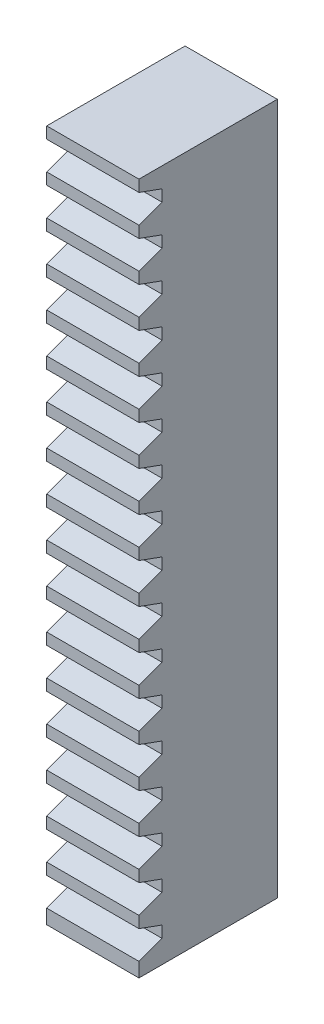
SolidWorks part; units mm, degrees
ref_plane "Alzado" through (0, 0, 0) normal (0, 0, 1) x (1, 0, 0)
ref_plane "Planta" through (0, 0, 0) normal (0, 1, 0) x (1, 0, 0)
ref_plane "Vista lateral" through (0, 0, 0) normal (1, 0, 0) x (0, 0, -1)
sketch "Croquis2" plane through (0, 0, 0) normal (0, 0, 1) x (1, 0, 0)
  line L0 (52.8503, 101.9015) -> (72.8503, 101.9015)
  line L1 (72.8503, 101.9015) -> (72.8503, -28.0985)
  line L15 (52.8503, -98.0985) -> (62.8503, -98.0985)
  line L16 (62.8503, -98.0985) -> (62.8503, -47.8388)
  line L17 (62.8503, -47.8388) -> (92.8503, -47.8388)
  line L18 (92.8503, -47.8388) -> (92.8503, -98.0985)
  line L19 (92.8503, -98.0985) -> (102.8503, -98.0985)
  line L20 (102.8503, -98.0985) -> (102.8503, -28.0985)
  line L21 (102.8503, -28.0985) -> (72.8503, -28.0985)
  line L22 (52.8503, 101.9015) -> (52.8503, -98.0985)
  dimension "D1" = 20
  dimension "D2" = 130
  dimension "D6" = 30
  dimension "D3" = 200
  dimension "D4" = 10
  dimension "D5" = 10
extrude "Saliente-Extruir1" add sketch "Croquis2" along normal blind 30
sketch "Croquis3" plane through (102.8503, 0, 0) normal (1, 0, 0) x (0, 0, -1)
  line L0 (-15, -83.0985) -> (-15, -98.0985) construction
  line L1 (-30, -98.0985) -> (0, -98.0985) construction
  circle A0 centre (-15, -83.0985) radius 6
  dimension "D1" = 15
extrude "Cortar-Extruir1" cut sketch "Croquis3" against normal blind 50
sketch "Croquis4" plane through (102.8503, 0, 0) normal (1, 0, 0) x (0, 0, -1)
  line L4 (-30, -98.0985) -> (0, -98.0985) construction
  line L6 (-30, -98.0985) -> (-30, -28.0985) construction
  line L11 (0, -98.0985) -> (0, -28.0985) construction
  line L14 (-20, -98.0985) -> (-30, -98.0985)
  line L15 (-30, -98.0985) -> (-30, -88.0985)
  line L16 (-10, -98.0985) -> (0, -98.0985)
  line L17 (0, -98.0985) -> (0, -88.0985)
  arc A3 (-30, -88.0985) -> (-20, -98.0985) centre (-20, -88.0985) ccw
  arc A4 (-10, -98.0985) -> (0, -88.0985) centre (-10, -88.0985) ccw
extrude "Cortar-Extruir2" cut sketch "Croquis4" against normal blind 50
sketch "Croquis5" plane through (52.8503, 0, 0) normal (-1, 0, 0) x (0, 0, 1)
  line L1 (30, 101.9015) -> (30, -88.0985) construction
  line L2 (30, 99.4015) -> (25, 97.5817)
  line L3 (25, 97.5817) -> (25, 95.0817)
  line L4 (25, 95.0817) -> (30, 93.2618)
  line L5 (30, 93.2618) -> (30, 99.4015)
  line L7 (30, 90.7618) -> (25, 88.942)
  line L8 (25, 88.942) -> (25, 86.442)
  line L9 (25, 86.442) -> (30, 84.6221)
  line L10 (30, 84.6221) -> (30, 90.7618)
  line L12 (30, 82.1221) -> (25, 80.3023)
  line L13 (25, 80.3023) -> (25, 77.8023)
  line L14 (25, 77.8023) -> (30, 75.9824)
  line L15 (30, 75.9824) -> (30, 82.1221)
  line L17 (30, 73.4824) -> (25, 71.6626)
  line L18 (25, 71.6626) -> (25, 69.1626)
  line L19 (25, 69.1626) -> (30, 67.3427)
  line L20 (30, 67.3427) -> (30, 73.4824)
  line L22 (30, 64.8427) -> (25, 63.0229)
  line L23 (25, 63.0229) -> (25, 60.5229)
  line L24 (25, 60.5229) -> (30, 58.703)
  line L25 (30, 58.703) -> (30, 64.8427)
  line L27 (30, 56.203) -> (25, 54.3831)
  line L28 (25, 54.3831) -> (25, 51.8831)
  line L29 (25, 51.8831) -> (30, 50.0633)
  line L30 (30, 50.0633) -> (30, 56.203)
  line L32 (30, 47.5633) -> (25, 45.7434)
  line L33 (25, 45.7434) -> (25, 43.2434)
  line L34 (25, 43.2434) -> (30, 41.4236)
  line L35 (30, 41.4236) -> (30, 47.5633)
  line L37 (30, 38.9236) -> (25, 37.1037)
  line L38 (25, 37.1037) -> (25, 34.6037)
  line L39 (25, 34.6037) -> (30, 32.7839)
  line L40 (30, 32.7839) -> (30, 38.9236)
  line L42 (30, 30.2839) -> (25, 28.464)
  line L43 (25, 28.464) -> (25, 25.964)
  line L44 (25, 25.964) -> (30, 24.1442)
  line L45 (30, 24.1442) -> (30, 30.2839)
  line L47 (30, 21.6442) -> (25, 19.8243)
  line L48 (25, 19.8243) -> (25, 17.3243)
  line L49 (25, 17.3243) -> (30, 15.5045)
  line L50 (30, 15.5045) -> (30, 21.6442)
  line L52 (30, 13.0045) -> (25, 11.1846)
  line L53 (25, 11.1846) -> (25, 8.6846)
  line L54 (25, 8.6846) -> (30, 6.8648)
  line L55 (30, 6.8648) -> (30, 13.0045)
  dimension "D2" = 2.5
  dimension "D3" = 110
  dimension "D4" = 110
  dimension "D5" = 5
  dimension "D6" = 2.5
extrude "Cortar-Extruir3" cut sketch "Croquis5" against normal blind 20
sketch "Croquis6" plane through (0, 0, 30) normal (0, 0, 1) x (1, 0, 0)
  line L0 (92.8503, -28.0985) -> (102.8503, -28.0985)
  line L2 (102.8503, -88.0985) -> (102.8503, -28.0985) construction
  line L3 (102.8503, -28.0985) -> (102.8503, -38.0985)
  line L4 (102.8503, -28.0985) -> (72.8503, -28.0985) construction
  arc A0 (102.8503, -38.0985) -> (92.8503, -28.0985) centre (92.8503, -38.0985) ccw
extrude "Cortar-Extruir4" cut sketch "Croquis6" against normal blind 30
sketch "Croquis7" plane through (0, 101.9015, 0) normal (0, 1, 0) x (1, 0, 0)
  line L0 (52.8503, 0) -> (52.8503, -30)
  line L1 (52.8503, -30) -> (72.8503, -30)
  line L2 (72.8503, -30) -> (72.8503, 0)
  line L3 (72.8503, 0) -> (52.8503, 0)
extrude "Saliente-Extruir2" add sketch "Croquis7" along normal blind 50
sketch "Croquis8" plane through (52.8503, 0, 0) normal (-1, 0, 0) x (0, 0, 1)
  line L0 (30, 99.4015) -> (30, 101.9015)
  line L1 (30, 151.9015) -> (30, 99.4015) construction
  line L2 (30, 101.9015) -> (25, 103.7214)
  line L3 (25, 103.7214) -> (25, 106.2214)
  line L4 (25, 106.2214) -> (30, 108.0412)
  line L5 (30, 108.0412) -> (30, 101.9015)
  line L6 (30, 108.0412) -> (30, 110.5412)
  line L7 (30, 110.5412) -> (25, 110.5412)
  line L8 (30, 110.5412) -> (25, 112.3611)
  line L9 (25, 112.3611) -> (25, 114.8611)
  line L10 (25, 114.8611) -> (30, 116.6809)
  line L11 (30, 116.6809) -> (30, 110.5412)
  line L12 (30, 119.1809) -> (25, 121.0008)
  line L13 (25, 121.0008) -> (25, 123.5008)
  line L14 (25, 123.5008) -> (30, 125.3206)
  line L15 (30, 125.3206) -> (30, 119.1809)
  line L16 (30, 127.8206) -> (25, 129.6405)
  line L17 (25, 129.6405) -> (25, 132.1405)
  line L18 (25, 132.1405) -> (30, 133.9603)
  line L19 (30, 133.9603) -> (30, 127.8206)
  line L20 (30, 136.4603) -> (25, 138.2802)
  line L21 (25, 138.2802) -> (25, 140.7802)
  line L22 (25, 140.7802) -> (30, 142.6)
  line L23 (30, 142.6) -> (30, 136.4603)
  line L24 (30, 145.1) -> (25, 146.9199)
  line L25 (25, 146.9199) -> (25, 149.4199)
  line L26 (25, 149.4199) -> (30, 151.2397)
  line L27 (30, 151.2397) -> (30, 145.1)
  point P5 (0, 0)
  point P31 (0, 0)
  dimension "D1" = 5
  dimension "D2" = 2.5
  dimension "D3" = 2.5
  dimension "D4" = 110
  dimension "D5" = 110
  dimension "D6" = 2.5
  dimension "D7" = 6
extrude "Cortar-Extruir6" cut sketch "Croquis8" against normal blind 20 contours L27 L26 L25 L24 | L23 L22 L21 L20 | L19 L18 L17 L16 | L15 L14 L13 L12 | L11 L10 L9 L8 | L5 L4 L3 L2 region at (52.8503, 113.6111, 27.8511) region at (52.8503, 104.9714, 27.8511) region at (52.8503, 122.2508, 27.8511) region at (52.8503, 130.8905, 27.8511) region at (52.8503, 139.5302, 27.8511) region at (52.8503, 148.1699, 27.8511)
sketch "Croquis9" plane through (0, 0, 30) normal (0, 0, 1) x (1, 0, 0)
  line L0 (52.8503, -88.0985) -> (62.8503, -88.0985)
  line L1 (62.8503, -88.0985) -> (62.8503, -98.0985)
  line L2 (62.8503, -98.0985) -> (52.8503, -98.0985)
  line L3 (52.8503, -98.0985) -> (52.8503, -88.0985)
  line L4 (92.8503, -88.0985) -> (102.8503, -88.0985)
  line L5 (102.8503, -88.0985) -> (102.8503, -98.0985)
  line L6 (102.8503, -98.0985) -> (92.8503, -98.0985)
  line L7 (92.8503, -98.0985) -> (92.8503, -88.0985)
extrude "Saliente-Extruir3" add sketch "Croquis9" against normal blind 30
sketch "Croquis10" plane through (102.8503, 0, 0) normal (1, 0, 0) x (0, 0, -1)
  line L0 (-30, -28.0985) -> (-30, -98.0985)
  line L1 (-30, -28.0985) -> (0, -28.0985)
  line L2 (0, -28.0985) -> (0, -98.0985)
  line L3 (0, -98.0985) -> (-30, -98.0985)
extrude "Saliente-Extruir4" add sketch "Croquis10" along normal blind 50
sketch "Croquis12" plane through (152.8503, 0, 0) normal (1, 0, 0) x (0, 0, -1)
  line L0 (0, -28.0985) -> (-30, -28.0985)
  line L1 (-30, -28.0985) -> (-30, -98.0985)
  line L2 (-30, -98.0985) -> (0, -98.0985)
  line L3 (0, -98.0985) -> (0, -28.0985)
extrude "Saliente-Extruir5" add sketch "Croquis12" against normal blind 100
sketch "Croquis13" plane through (0, 0, 30) normal (0, 0, 1) x (1, 0, 0)
  line L0 (52.8503, 6.8648) -> (72.8503, 6.8648)
  line L1 (52.8503, 6.8648) -> (52.8503, -98.0985) construction
  line L2 (72.8503, 6.8648) -> (52.8503, 6.8648) construction
  line L3 (72.8503, 6.8648) -> (72.8503, -28.0985)
  line L4 (72.8503, -28.0985) -> (152.8503, -28.0985)
  line L5 (152.8503, -28.0985) -> (152.8503, -98.0985)
  line L6 (152.8503, -98.0985) -> (52.8503, -98.0985)
  line L7 (52.8503, -98.0985) -> (52.8503, 6.8648)
extrude "Saliente-Extruir6" add sketch "Croquis13" along normal blind 80
sketch "Croquis15" plane through (0, -28.0985, 0) normal (0, 1, 0) x (1, 0, 0)
  line L0 (72.8503, 0) -> (152.8503, 0)
  line L1 (72.8503, -110) -> (72.8503, 0) construction
  line L2 (152.8503, 0) -> (72.8503, 0) construction
  line L3 (152.8503, 0) -> (152.8503, -110)
  line L4 (152.8503, -110) -> (72.8503, -110)
  line L5 (72.8503, -110) -> (72.8503, 0)
extrude "Saliente-Extruir7" add sketch "Croquis15" along normal blind 30
sketch "Croquis16" plane through (0, 6.8648, 0) normal (0, 1, 0) x (1, 0, 0)
  line L0 (52.8503, -110) -> (72.8503, -110)
  line L1 (72.8503, -110) -> (72.8503, -30)
  line L2 (72.8503, -30) -> (52.8503, -30)
  line L3 (52.8503, -30) -> (52.8503, -110)
extrude "Cortar-Extruir7" cut sketch "Croquis16" against normal up to vertex (4.9633 mm away) up to point (72.8503, 1.9015, 0)
sketch "Croquis17" plane through (52.8503, 0, 0) normal (-1, 0, 0) x (0, 0, 1)
  line L2 (110, 1.9015) -> (110, -98.0985)
  line L3 (0, -98.0985) -> (77.3858, -98.0985)
  line L4 (30, 1.9015) -> (110, 1.9015)
  line L5 (68.8909, -79.4158) -> (0, -10.5249)
  line L6 (30, 1.9015) -> (90.1041, -58.2026)
  line L7 (0, -10.5249) -> (0, -98.0985)
  line L8 (0, 151.9015) -> (0, -98.0985) construction
  line L10 (77.3858, -98.0985) -> (110, -98.0985)
  arc A1 (68.8909, -79.4158) -> (90.1041, -58.2026) centre (79.4975, -68.8092) ccw
  dimension "D1" = 85
  dimension "D3" = 30
extrude "Cortar-Extruir8" cut sketch "Croquis17" against normal blind 100
sketch "Croquis19" plane through (0, 0, 0) normal (0, 1, 0) x (1, 0, 0)
  line L0 (52.8503, -94.4975) -> (57.8503, -94.4975)
  line L1 (52.8503, -94.4975) -> (152.8503, -94.4975) construction
  line L2 (57.8503, -94.4975) -> (57.8503, -44.1182)
  line L3 (57.8503, -44.1182) -> (88.8503, -44.1182)
  line L4 (88.8503, -44.1182) -> (88.8503, -94.4975)
  line L5 (88.8503, -94.4975) -> (93.8503, -94.4975)
  line L6 (93.8503, -94.4975) -> (93.8503, -30)
  line L7 (152.8503, -30) -> (72.8503, -30) construction
  line L8 (93.8503, -30) -> (93.8503, 4.7181)
  line L9 (93.8503, 4.7181) -> (155.9644, 4.7181)
  line L10 (155.9644, 4.7181) -> (155.9644, -98.5037)
  line L11 (155.9644, -98.5037) -> (93.8503, -98.5037)
  line L13 (52.8503, -30) -> (52.8503, -94.4975)
  line L14 (93.8503, -98.5037) -> (93.8503, -94.4975)
  dimension "D1" = 5
  dimension "D2" = 5
  dimension "D3" = 31
extrude "Cortar-Extruir10" cut sketch "Croquis19" against normal through all both and the other way through all contours L14 L11 L10 L9 L8 L6 region at (124.9074, 0, 46.8928)
sketch "Croquis22" plane through (93.8503, 0, 0) normal (1, 0, 0) x (0, 0, -1)
  line L0 (-90.1041, -58.2026) -> (-68.8909, -79.4158)
  circle A0 centre (-79.4975, -68.8092) radius 6
  dimension "D1" = 12
extrude "Cortar-Extruir14" cut sketch "Croquis22" against normal blind 100 contours L0 A0 | L0 A0 region at (93.8503, -67.0085, 77.6968) region at (93.8503, -70.6098, 81.2981)
sketch "Croquis24" plane through (72.8503, 0, 0) normal (1, 0, 0) x (0, 0, -1)
  line L0 (-30, 151.2397) -> (0, 151.2397)
  line L1 (0, 1.9015) -> (0, 151.9015) construction
  line L2 (0, 151.2397) -> (0, 153.7397)
  line L3 (0, 153.7397) -> (-30, 153.7397)
  line L4 (-30, 153.7397) -> (-30, 151.2397)
  dimension "D1" = 2.5
extrude "Saliente-Extruir8" add sketch "Croquis24" against normal blind 20
ref_plane "Plano3" through (0, 1.9015, 0) normal (0, 1, 0) x (1, 0, 0)
sketch "Croquis25" plane through (0, 1.9015, 0) normal (0, 1, 0) x (1, 0, 0)
  line L0 (52.8503, -94.4975) -> (57.8503, -94.4975)
  line L1 (52.8503, -94.4975) -> (93.8503, -94.4975) construction
  line L2 (57.8503, -94.4975) -> (57.8503, -44.4975)
  line L3 (57.8503, -44.4975) -> (88.8503, -44.4975)
  line L4 (88.8503, -44.4975) -> (88.8503, -94.4975)
  line L5 (88.8503, -94.4975) -> (57.8503, -94.4975)
  line L6 (93.8503, -94.4975) -> (93.8503, -68.8909) construction
  dimension "D1" = 5
  dimension "D2" = 5
  dimension "D3" = 31
  dimension "D4" = 50
extrude "Cortar-Extruir15" cut sketch "Croquis25" against normal blind 100 contours L5 L4 L3 L2 region at (73.3503, 1.9015, 69.4975)
sketch "Croquis26" plane through (0, 15.9508, 15.9508) normal (0, 0.7071, 0.7071) x (1, 0, 0)
  line L3 (88.8503, -104.8686) -> (88.8503, -40.3712) construction
  line L4 (88.8503, -90.3712) -> (57.8503, -90.3712)
  line L5 (57.8503, -40.3712) -> (57.8503, -104.8686) construction
  line L6 (57.8503, -90.3712) -> (57.8503, -40.3712)
  line L7 (88.8503, -90.3712) -> (88.8503, -40.3712)
  line L8 (88.8503, -40.3712) -> (57.8503, -40.3712)
  dimension "D1" = 50
extrude "Cortar-Extruir17" cut sketch "Croquis26" against normal blind 100
ref_plane "Plano4" through (52.8503, 0, 0) normal (-1, 0, 0) x (0, 0, 1)
sketch "Croquis27" plane through (52.8503, 0, 0) normal (-1, 0, 0) x (0, 0, 1)
  line L0 (79.4975, -68.8092) -> (15, -68.8092)
  line L1 (15, 153.7397) -> (15, -68.8092)
  line L2 (0, 153.7397) -> (30, 153.7397) construction
  line L3 (79.4975, -83.8092) -> (94.4975, -83.8092)
  line L4 (94.4975, -83.8092) -> (94.4975, 153.7397)
  line L5 (0, 153.7397) -> (0, -10.5249) construction
  line L6 (94.4975, -83.8092) -> (79.4975, -68.8092) construction
  line L7 (79.4975, -68.8092) -> (33.5028, -22.8145) construction
  line L8 (79.4975, -68.8092) -> (102.4948, -45.8118) construction
  line L9 (102.4948, -45.8118) -> (58.6156, -89.6911) construction
  line L10 (0, 153.7397) -> (30, 153.7397)
  line L11 (30, 153.7397) -> (30, 1.9015)
  line L12 (30, 1.9015) -> (90.1041, -58.2026)
  line L13 (90.1041, -58.2026) -> (83.7401, -64.5665)
  line L14 (68.8909, -79.4158) -> (75.2548, -73.0518)
  line L15 (68.8909, -79.4158) -> (0, -10.5249)
  line L16 (0, -10.5249) -> (0, 153.7397)
  line L18 (27.5, 1.9015) -> (27.5, 153.7397)
  arc A0 (68.8909, -79.4158) -> (90.1041, -58.2026) centre (79.4975, -68.8092) ccw construction
  dimension "D1" = 64.4975
  dimension "D2" = 222.5489
  dimension "D3" = 237.5489
  dimension "D4" = 94.4975
  dimension "D5" = 45
  dimension "D6" = 79.4975
  dimension "D7" = 2.5
ref_axis "Eje1" through (104.2041, -68.8092, 79.4975) along (-1, 0, 0)
sketch "Croquis29" plane through (52.8503, 0, 0) normal (-1, 0, 0) x (0, 0, 1)
  line L0 (30, 1.9015) -> (0, 1.9015)
  line L1 (0, 153.7397) -> (0, -10.5249) construction
  line L2 (0, 1.9015) -> (0, -95.8631)
  line L3 (0, -95.8631) -> (119.4239, -95.8631)
  line L4 (119.4239, -95.8631) -> (119.4239, 1.9015)
  line L5 (119.4239, 1.9015) -> (0, 1.9015)
extrude "Cortar-Extruir18" cut sketch "Croquis29" against normal blind 100 contours L4 L5 L0 L2 L3 region at (52.8503, -46.9808, 59.712)
sketch "Croquis30" plane through (52.8503, 0, 0) normal (-1, 0, 0) x (0, 0, 1)
  line L0 (0, 153.7397) -> (0, 3.7397)
  line L1 (0, 153.7397) -> (0, 1.9015) construction
  line L2 (0, 3.7397) -> (30, 3.7397)
  line L3 (30, 1.9015) -> (30, 6.8648) construction
  line L4 (30, 3.7397) -> (30, 1.9015)
  line L5 (30, 1.9015) -> (0, 1.9015)
  line L6 (0, 1.9015) -> (0, 3.7397)
  dimension "D1" = 150
extrude "Cortar-Extruir19" cut sketch "Croquis30" against normal blind 100 contours L6 L5 L4 L2 region at (52.8503, 2.8206, 15)
